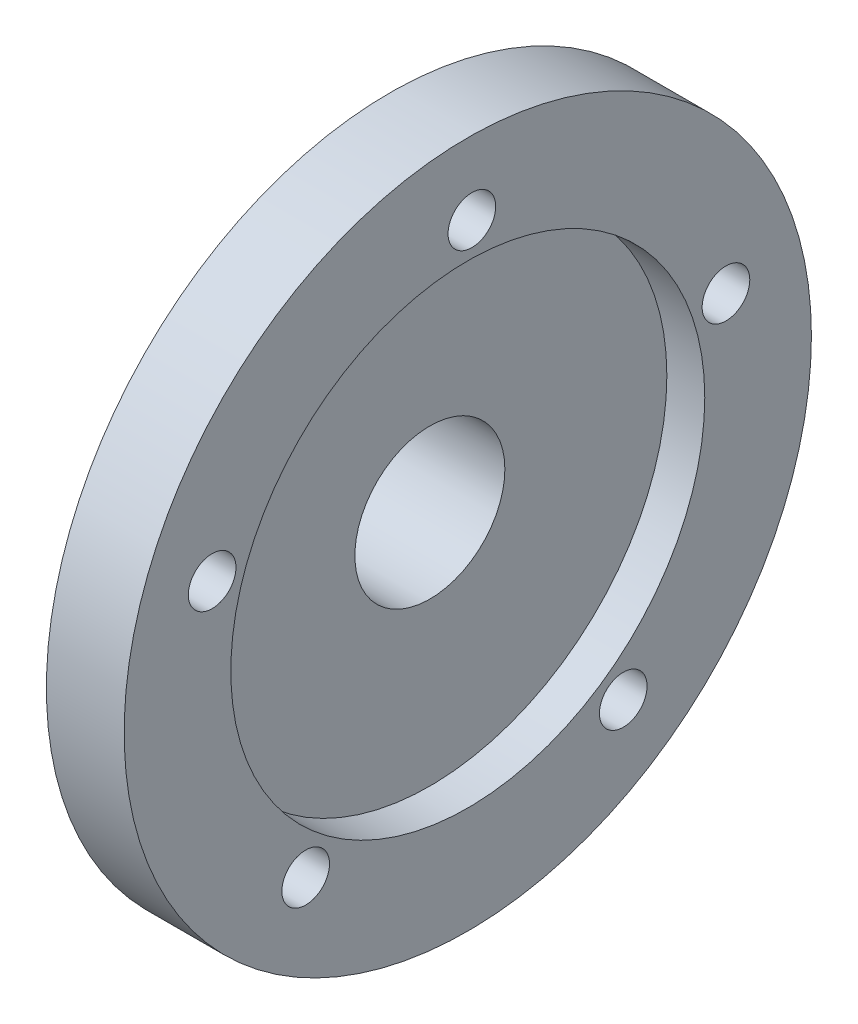
SolidWorks part; units mm, degrees
material "6061 Alloy"
ref_plane "Front Plane" through (0, 0, 0) normal (0, 0, 1) x (1, 0, 0)
ref_plane "Top Plane" through (0, 0, 0) normal (0, 1, 0) x (1, 0, 0)
ref_plane "Right Plane" through (0, 0, 0) normal (1, 0, 0) x (0, 0, -1)
sketch "Sketch1" plane through (0, 0, 0) normal (0, 0, 1) x (1, 0, 0)
  line L0 (0, 0) -> (-647.0721, 0) construction
  line L1 (-27.8573, 8.0391) -> (-14.0241, 8.0391)
  line L2 (-14.0241, 8.0391) -> (-14.0241, 25.4)
  line L3 (-14.0241, 25.4) -> (-9.9601, 25.4)
  line L5 (-18.2958, 17.8013) -> (-27.8573, 17.8013) construction
  line L6 (-27.8573, 17.8013) -> (-27.8573, 8.0391)
  line L7 (-9.9601, 25.4) -> (-9.9601, 36.83)
  line L8 (-9.9601, 36.83) -> (-18.2958, 36.83)
  line L10 (-12.8446, -23.9061) -> (-22.4061, -23.9061) construction
  line L11 (-4.5089, -34.3169) -> (-12.8446, -34.3169) construction
  line L12 (-18.2958, 36.83) -> (-27.8573, 17.8013)
  dimension "D1" = 16.0782
  dimension "D2" = 50.8
  dimension "D3" = 4.064
  dimension "D4" = 73.66
revolve "Revolve1" add sketch "Sketch1" angle 360 about L0
sketch "Sketch2" plane through (-9.9601, 0, 0) normal (1, 0, 0) x (0, 0, -1)
  circle A0 centre (27.6711, 8.5299) radius 2.032 construction
  circle A1 centre (0.4385, 28.9527) radius 2.032 construction
  circle A2 centre (-27.4001, 9.3639) radius 2.032 construction
  circle A3 centre (-17.3727, -23.1655) radius 2.032 construction
  circle A4 centre (16.6632, -23.6809) radius 2.032 construction
  circle A5 centre (27.6711, 8.5299) radius 2.032 construction
  circle A6 centre (0.4385, 28.9527) radius 2.032 construction
  circle A7 centre (-27.4001, 9.3639) radius 2.032 construction
  circle A8 centre (-17.3727, -23.1655) radius 2.032 construction
  circle A9 centre (16.6632, -23.6809) radius 2.032 construction
  circle A10 centre (16.6632, -23.6809) radius 2.5527
  circle A11 centre (-17.3727, -23.1655) radius 2.5527
  circle A12 centre (0.4385, 28.9527) radius 2.5527
  circle A13 centre (27.6711, 8.5299) radius 2.5527
  circle A14 centre (-27.4001, 9.3639) radius 2.5527
  dimension "D1" = 5.1054
extrude "Cut-Extrude1" cut sketch "Sketch2" against normal through all
